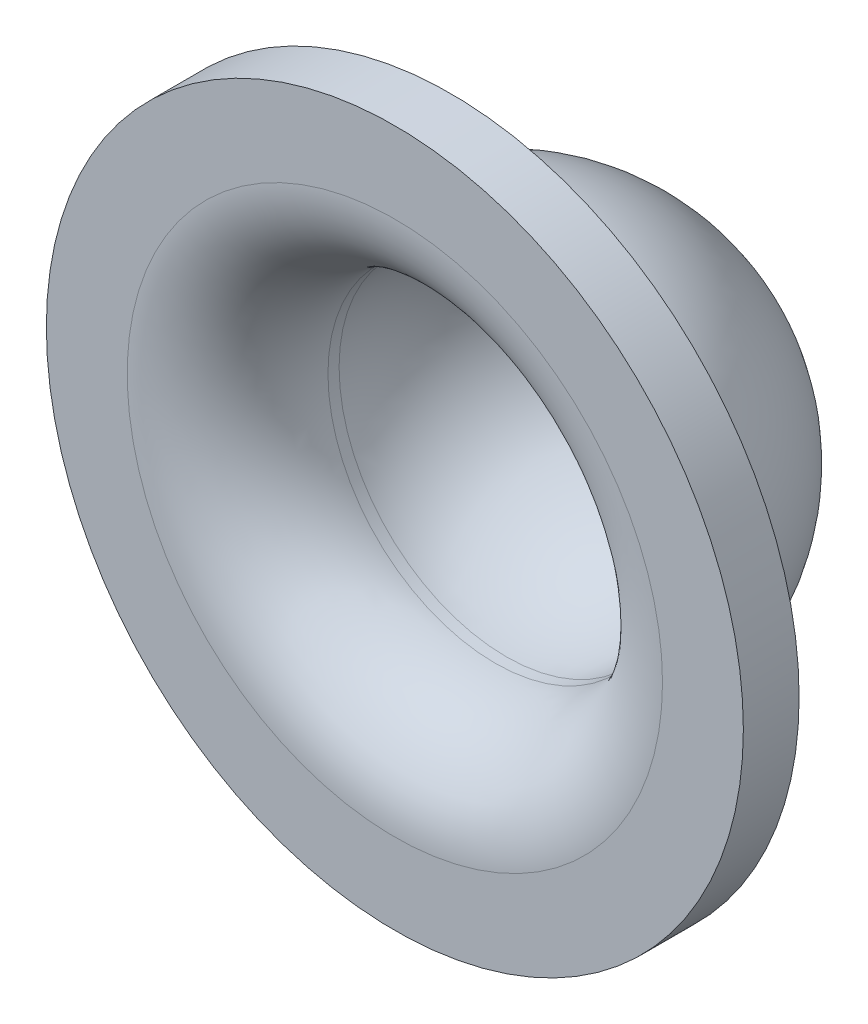
SolidWorks part; units mm, degrees
material "Резина"
ref_plane "Спереди" through (0, 0, 0) normal (0, 0, 1) x (1, 0, 0)
ref_plane "Сверху" through (0, 0, 0) normal (0, 1, 0) x (1, 0, 0)
ref_plane "Справа" through (0, 0, 0) normal (1, 0, 0) x (0, 0, -1)
sketch "Эскиз1" plane through (0, 0, 0) normal (0, 1, 0) x (1, 0, 0)
  line L0 (0, 1) -> (0, 6.2181)
  line L1 (0, 0) -> (6.25, 0)
  line L2 (0, 0) -> (0, 1)
  line L3 (0, 1) -> (3.873, 1)
  line L4 (6.25, 0) -> (6.25, 1)
  line L5 (4, 2) -> (4, 1.8)
  line L6 (4.8, 1) -> (6.25, 1)
  circle A0 centre (0, 2) radius 4
  arc A1 (4, 1.8) -> (4.8, 1) centre (4.8, 1.8) ccw
  point P13 (4, 1)
  dimension "D3" = 8
  dimension "D5" = 0.8
  dimension "D1" = 1
  dimension "D2" = 6.25
  dimension "D4" = 1
revolve "Повернуть1" add sketch "Эскиз1" angle 360 about L0 region at (1.8494, 0, -0.5092) region at (1.7651, 0, -3.1719) region at (4.9145, 0, -0.5332)
shell "Оболочка1" thickness 1 removed face at (6.25, 0, 0)
